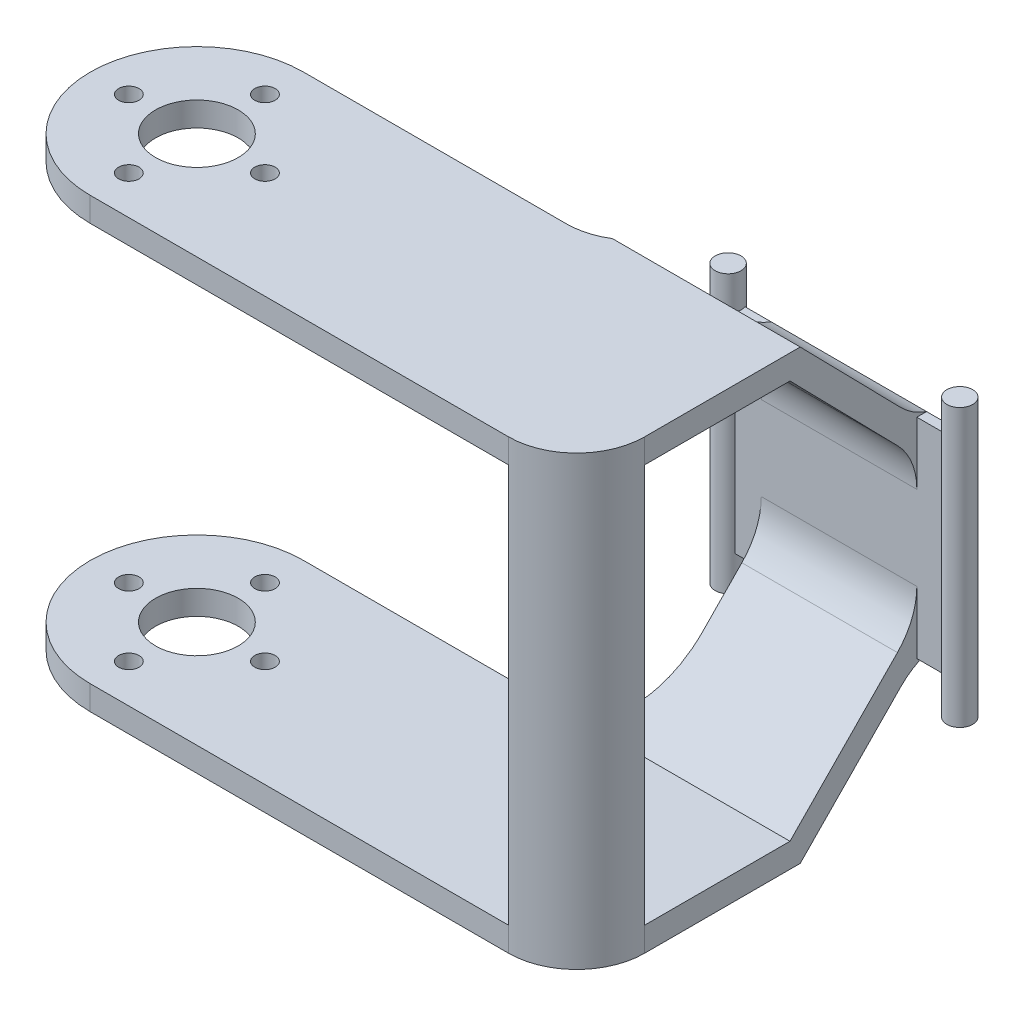
SolidWorks part; units mm, degrees
ref_plane "Front Plane" through (0, 0, 0) normal (0, 0, 1) x (1, 0, 0)
ref_plane "Top Plane" through (0, 0, 0) normal (0, 1, 0) x (1, 0, 0)
ref_plane "Right Plane" through (0, 0, 0) normal (1, 0, 0) x (0, 0, -1)
sketch "Sketch1" plane through (0, 0, 0) normal (0, 1, 0) x (1, 0, 0)
  line L1 (11.915, 0.5) -> (-11.915, 0.5)
  line L2 (11.915, 0.5) -> (11.915, -0.5)
  line L3 (11.915, -0.5) -> (-11.915, -0.5)
  line L4 (-11.915, 0.5) -> (-11.915, -0.5)
  line L5 (11.915, 0.5) -> (-11.915, -0.5) construction
  line L6 (11.915, -0.5) -> (-11.915, 0.5) construction
  point P0 (0, 0)
  dimension "D1" = 23.83
  dimension "D3" = 1
extrude "Boss-Extrude1" add sketch "Sketch1" along normal blind 21.5
ref_plane "Plane1" through (0, 10.75, 0) normal (0, 1, 0) x (1, 0, 0)
sketch "Sketch2" plane through (0, 10.75, 0) normal (0, 1, 0) x (1, 0, 0)
  line L0 (11.915, -0.5) -> (11.915, 0.5) construction
  line L1 (-11.915, 0.5) -> (-11.915, -0.5) construction
  line L2 (11.915, -0.5) -> (11.915, 0.5) construction
  line L3 (-11.915, 0.5) -> (-11.915, -0.5) construction
  circle A0 centre (-11.915, 0) radius 1.325
  circle A1 centre (11.915, 0) radius 1.325
  dimension "D1" = 2.65
extrude "Boss-Extrude2" add sketch "Sketch2" along normal mid plane 28.5
sketch "Sketch3" plane through (0, 21.5, 0) normal (0, 1, 0) x (1, 0, 0)
  line L0 (-10.688, -0.5) -> (10.688, -0.5) construction
  line L1 (-7.5, -0.5) -> (7.5, -0.5)
  line L2 (-7.5, -0.5) -> (-7.5, -26.5)
  line L3 (-7.5, -26.5) -> (7.5, -26.5)
  line L4 (7.5, -0.5) -> (7.5, -26.5)
  line L5 (0, -1000) -> (0, 49000) construction
  line L6 (-7.5, -26.5) -> (-32.5, -26.5)
  line L7 (-7.5, -26.5) -> (-7.5, -3.5)
  line L8 (-7.5, -3.5) -> (-32.5, -3.5)
  line L9 (-32.5, -26.5) -> (-32.5, -3.5)
  line L11 (-4.5, -3.5) -> (4.5, -3.5)
  line L12 (4.5, -3.5) -> (4.5, -23.5)
  line L13 (-4.5, -23.5) -> (4.5, -23.5)
  line L14 (-10.5, -23.5) -> (-29.5, -23.5)
  line L16 (-10.5, -6.5) -> (-29.5, -6.5)
  line L18 (-29.5, -23.5) -> (-29.5, -6.5) construction
  line L19 (-10.5, -23.5) -> (-10.5, -6.5) construction
  line L20 (-4.5, -3.5) -> (-4.5, -23.5) construction
  line L21 (-4.5, -3.5) -> (-4.5, -6.5)
  line L22 (-4.5, -6.5) -> (-10.5, -6.5)
  line L23 (-4.5, -23.5) -> (-10.5, -23.5)
  line L24 (-18.5, -6.5) -> (-18.5, -23.5)
  circle A0 centre (-32.5, -15) radius 11.5
  circle A1 centre (-32.5, -15) radius 4.25
  circle A2 centre (-32.5, -15) radius 7 construction
  circle A3 centre (-32.5, -8) radius 1.05
  circle A4 centre (-25.5, -15) radius 1.05
  circle A5 centre (-32.5, -22) radius 1.05
  circle A6 centre (-39.5, -15) radius 1.05
  point P10 (0, -0.5)
  line M14 (-10.688, -0.5) -> (10.688, -0.5)
  dimension "D5" = 8.5
  dimension "D6" = 14
  dimension "D7" = 2.1
  dimension "D1" = 15
  dimension "D2" = 26
  dimension "D3" = 23
  dimension "D4" = 25
  dimension "D9" = 14
  dimension "D8" = 3
extrude "Boss-Extrude3" [suppressed] add sketch "Sketch3" against normal up to surface (18.5 mm away) contours L4 L2 L3 M14 | A0 L6 L2 L8 | A5 L9 A0 A3 A1 A4 | A5 L9 A1 A3 A0 A6 | A0 L16 L22 L2 L8 | A0 L6 L2 L23 L14
sketch "Sketch4" plane through (0, 0, 0) normal (1, 0, 0) x (0, 0, -1)
  line L0 (-0.5, 21.5) -> (-12.5, 33.75)
  line L1 (-12.5, 33.75) -> (-35.5, 33.75)
  line L2 (-35.5, 33.75) -> (-35.5, 31.25)
  line L3 (-35.5, 31.25) -> (-13.5507, 31.25)
  line L4 (-13.5507, 31.25) -> (-0.5, 17.9274)
  line L5 (-0.5, 21.5) -> (-0.5, 0) construction
  line L6 (-0.5, 21.5) -> (-0.5, 0)
  line L7 (-0.5, 0) -> (-12.5, -12.25)
  line L8 (-12.5, -12.25) -> (-35.5, -12.25)
  line L9 (-35.5, -12.25) -> (-35.5, -9.75)
  line L10 (-35.5, -9.75) -> (-13.5507, -9.75)
  line L11 (-13.5507, -9.75) -> (-0.5, 3.5726)
  line L12 (-1000.5, 10.75) -> (48999.5, 10.75) construction
  line L13 (-35.5, 31.25) -> (-35.5, -9.75) construction
  point P3 (-35.5, 10.75)
  point P20 (-0.5, 10.75)
  dimension "D1" = 2.5
  dimension "D2" = 41
  dimension "D3" = 23
  dimension "D4" = 2.5
  dimension "D5" = 35
  dimension "D6" = 2.5
extrude "Boss-Extrude4" add sketch "Sketch4" along normal mid plane 16 contours L6 L0 L1 L2 L3 L4 | L11 L10 L9 L8 L7 L6
sketch "Sketch5" plane through (-8, 0, 0) normal (-1, 0, 0) x (0, 0, 1)
  line L1 (35.5, 33.75) -> (13.5507, 33.75)
  line L2 (35.5, 33.75) -> (35.5, 31.25)
  line L3 (35.5, 31.25) -> (13.5507, 31.25)
  line L4 (13.5507, 33.75) -> (13.5507, 31.25)
  line L5 (35.5, -12.25) -> (13.5507, -12.25)
  line L6 (35.5, -12.25) -> (35.5, -9.75)
  line L7 (35.5, -9.75) -> (13.5507, -9.75)
  line L8 (13.5507, -12.25) -> (13.5507, -9.75)
extrude "Boss-Extrude5" add sketch "Sketch5" along normal blind 45
sketch "Sketch6" plane through (0, 33.75, 0) normal (0, 1, 0) x (1, 0, 0)
  line L0 (-42.0253, -13.5507) -> (-42.0253, -35.5) construction
  line L1 (-53, -13.5507) -> (-8, -13.5507) construction
  line L2 (8, -35.5) -> (-53, -35.5) construction
  line L3 (-53, -24.5253) -> (8, -24.5253) construction
  line L4 (-53, -35.5) -> (-53, -13.5507) construction
  line L5 (8, -12.5) -> (8, -35.5) construction
  line L6 (-42.0253, -13.5507) -> (-53, -13.5507)
  line L7 (-53, -13.5507) -> (-53, -35.5)
  line L8 (-53, -35.5) -> (-42.0253, -35.5)
  circle A0 centre (-42.0253, -24.5253) radius 10.9747
  circle A1 centre (-42.0253, -24.5253) radius 4.25
  circle A2 centre (-42.0253, -24.5253) radius 7 construction
  circle A3 centre (-42.0253, -17.5253) radius 1.05
  circle A4 centre (-35.0253, -24.5253) radius 1.05
  circle A5 centre (-42.0253, -31.5253) radius 1.05
  circle A6 centre (-49.0253, -24.5253) radius 1.05
  point P12 (-42.0253, -24.5253)
  line M9 (-8, -13.5507) -> (-53, -13.5507)
  line M10 (-53, -13.5507) -> (-53, -35.5)
  line M11 (-53, -35.5) -> (8, -35.5)
  dimension "D1" = 8.5
  dimension "D2" = 14
  dimension "D3" = 2.1
extrude "Cut-Extrude1" cut sketch "Sketch6" against normal through all contours A1 | A6 | A3 | A4 | A5 | A0 M9 M10 | A0 L7 M11
fillet "Fillet1" radius 7 4 edges at (-8, -11, 13.5507) (-8, 32.5, 13.5507) (8, -11, 35.5) (8, 32.5, 35.5)
fillet "Fillet2" radius 7 2 edges at (0, 3.5726, 0.5) (0, 17.9274, 0.5)
fillet "Fillet3" radius 7 2 edges at (0, 21.5, 0.5) (0, 0, 0.5)
sketch "Sketch8" plane through (0, -9.75, 0) normal (0, 1, 0) x (1, 0, 0)
  line L0 (-42.0253, -13.5507) -> (-15, -13.5507) construction
  line L1 (-42.0253, -13.5507) -> (-15, -13.5507)
  line L2 (8, -28.5) -> (5, -28.5)
  line L3 (1, -35.5) -> (1, -32.5)
  arc A0 (-15, -13.5507) -> (-8, -6.5507) centre (-15, -6.5507) ccw construction
  arc A1 (1, -35.5) -> (8, -28.5) centre (1, -28.5) ccw construction
  arc A2 (-15, -13.5507) -> (-8, -6.5507) centre (-15, -6.5507) ccw
  arc A3 (1, -35.5) -> (8, -28.5) centre (1, -28.5) ccw
  circle A4 centre (-1.5277, -25.9723) radius 7
  arc M10 (1, -35.5) -> (8, -28.5) centre (1, -28.5) ccw
  dimension "D1" = 3
extrude "Boss-Extrude6" add sketch "Sketch8" along normal up to surface (41 mm away) contours A4 L3 L2 M10 up to face at (-42.0253, 31.25, 28.7753)
equation "\"D4@Sketch4\"=\"D1@Sketch4\""
equation "\"D6@Sketch4\"=\"D1@Sketch4\""
